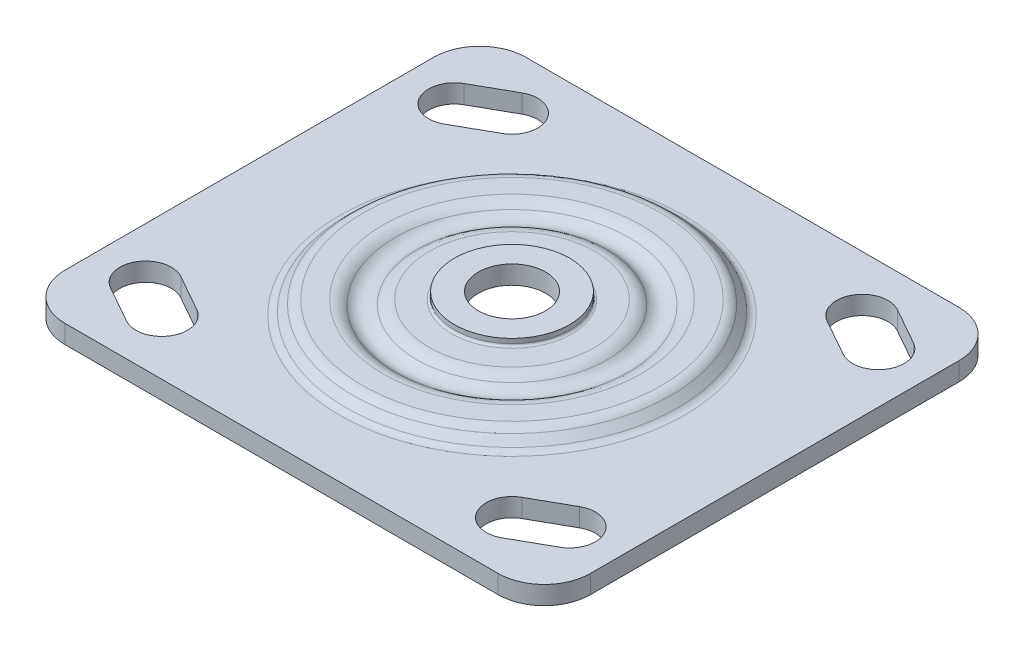
SolidWorks part; units mm, degrees
ref_plane "Front Plane" through (0, 0, 0) normal (0, 0, 1) x (1, 0, 0)
ref_plane "Top Plane" through (0, 0, 0) normal (0, 1, 0) x (1, 0, 0)
ref_plane "Right Plane" through (0, 0, 0) normal (1, 0, 0) x (0, 0, -1)
ref_axis "Axis_X" through (-88.99, 0, 0) along (1, 0, 0)
ref_axis "Axis_Y" through (0, 55, 0) along (0, -1, 0)
ref_axis "Axis_Z" through (0, 0, -88.99) along (0, 0, 1)
sketch "Sketch1" plane through (0, 0, 0) normal (0, 0, 1) x (1, 0, 0)
  line L0 (0, 0) -> (0, 8.505) construction
  line L1 (0, 8.505) -> (-12.5, 8.505)
  line L2 (-12.5, 8.505) -> (-12.5, 7.5)
  line L3 (-13, 7) -> (-18.011, 7)
  line L4 (-27.989, 7) -> (-32.41, 7)
  line L5 (-34.4607, 6.1506) -> (-35.996, 4.6151)
  line L6 (-37.481, 4) -> (-37.481, 0)
  line L7 (-31.747, 3) -> (-28.1759, 3)
  line L8 (-33.168, 1.7863) -> (-32.1005, 2.8536)
  line L9 (-18.011, 3) -> (-13.938, 3)
  line L10 (-12.0015, 4.5) -> (0, 4.5)
  line L11 (0, 8.505) -> (0, 4.5)
  arc A0 (-18.011, 7) -> (-20.6718, 5.9867) centre (-18.011, 3) ccw
  arc A1 (-25.3282, 5.9867) -> (-20.6718, 5.9867) centre (-23, 8.6) ccw
  arc A2 (-25.3282, 5.9867) -> (-27.989, 7) centre (-27.989, 3) ccw
  arc A3 (-37.481, 0) -> (-33.168, 1.7863) centre (-37.481, 6.1) ccw
  arc A4 (-32.41, 7) -> (-34.4607, 6.1506) centre (-32.41, 4.1) ccw
  arc A5 (-31.747, 3) -> (-32.1005, 2.8536) centre (-31.747, 2.5) ccw
  arc A6 (-27.8524, 2.8812) -> (-18.011, 3) centre (-23, 8.6) ccw
  arc A7 (-27.8524, 2.8812) -> (-28.1759, 3) centre (-28.1759, 2.5) ccw
  arc A9 (-13.938, 3) -> (-12.4856, 4.125) centre (-13.938, 4.5) ccw
  arc A10 (-12.0015, 4.5) -> (-12.4856, 4.125) centre (-12.0015, 4) ccw
  arc A11 (-37.481, 4) -> (-35.996, 4.6151) centre (-37.481, 6.1) ccw
  arc A12 (-12.5, 7.5) -> (-13, 7) centre (-13, 7.5) cw
  point P35 (-12.438, 4.5)
  dimension "FIX_3" = 8
  dimension "FIX_5" = 7
  dimension "FIX_7" = 2.9
  dimension "FIX_9" = 12.2
  dimension "FIX_10" = 0.5
  dimension "FIX_12" = 0.5
  dimension "FIX_13" = 3
  dimension "FIX_14" = 0.5
  dimension "FIX_15" = 0.5
  dimension "FIX_16" = 25
  dimension "FIX_1" = 8.505
  dimension "FIX_2" = 7
  dimension "FIX_4" = 18.011
  dimension "FIX_17" = 23
  dimension "FIX_18" = 74.962
  dimension "FIX_6" = 4
  dimension "FIX_8" = 5.071
  dimension "FIX_11" = 5.734
  dimension "FIX_19" = 13.938
revolve "Revolve1" add sketch "Sketch1" angle 360 about L0
sketch "Sketch2" plane through (0, 0, 0) normal (0, 1, 0) x (1, 0, 0)
  line L0 (-46, 33.5) -> (-38, 38) construction
  line L1 (-57, -50) -> (57, -50)
  line L2 (-57, -50) -> (-57, 50)
  line L3 (-57, 50) -> (57, 50)
  line L4 (57, -50) -> (57, 50)
  line L5 (-57, -50) -> (57, 50) construction
  line L6 (-57, 50) -> (57, -50) construction
  line L7 (-48.7455, 38.3808) -> (-40.7455, 42.8808)
  line L8 (-43.2545, 28.6192) -> (-35.2545, 33.1192)
  line L9 (46, -33.5) -> (38, -38) construction
  line L10 (48.7455, -38.3808) -> (40.7455, -42.8808)
  line L11 (43.2545, -28.6192) -> (35.2545, -33.1192)
  line L12 (38, 38) -> (46, 33.5) construction
  line L13 (40.7455, 42.8808) -> (48.7455, 38.3808)
  line L14 (35.2545, 33.1192) -> (43.2545, 28.6192)
  line L15 (-46, -33.5) -> (-38, -38) construction
  line L16 (-43.2545, -28.6192) -> (-35.2545, -33.1192)
  line L17 (-48.7455, -38.3808) -> (-40.7455, -42.8808)
  line L18 (0, 0) -> (57, 0) construction
  line L19 (0, 0) -> (0, 50) construction
  circle A0 centre (0, 0) radius 37.481 construction
  circle A1 centre (0, 0) radius 37.481
  arc A2 (-48.7455, 38.3808) -> (-43.2545, 28.6192) centre (-46, 33.5) ccw
  arc A3 (-35.2545, 33.1192) -> (-40.7455, 42.8808) centre (-38, 38) ccw
  arc A4 (48.7455, -38.3808) -> (43.2545, -28.6192) centre (46, -33.5) ccw
  arc A5 (35.2545, -33.1192) -> (40.7455, -42.8808) centre (38, -38) ccw
  arc A6 (40.7455, 42.8808) -> (35.2545, 33.1192) centre (38, 38) ccw
  arc A7 (43.2545, 28.6192) -> (48.7455, 38.3808) centre (46, 33.5) ccw
  arc A8 (-43.2545, -28.6192) -> (-48.7455, -38.3808) centre (-46, -33.5) ccw
  arc A9 (-40.7455, -42.8808) -> (-35.2545, -33.1192) centre (-38, -38) ccw
  point P9 (-42, 35.75)
  point P16 (42, -35.75)
  point P23 (42, 35.75)
  point P30 (-42, -35.75)
  dimension "FIX_21" = 114
  dimension "FIX_22" = 100
  dimension "FIX_23" = 11.2
  dimension "FIX_24" = 8
  dimension "FIX_25" = 4.5
  dimension "FIX_26" = 67
  dimension "FIX_27" = 76
  dimension "FIX_28" = 76
  dimension "FIX_29" = 67
extrude "Boss-Extrude1" add sketch "Sketch2" along normal blind 4
fillet "Fillet1" radius 10 4 edges at (-57, 2, -50) (57, 2, -50) (57, 2, 50) (-57, 2, 50)
sketch "Sketch3" plane through (0, 8.505, 0) normal (0, 1, 0) x (1, 0, 0)
  circle A0 centre (0, 0) radius 7.3
  dimension "FIX_32" = 14.6
extrude "Cut-Extrude1" cut sketch "Sketch3" against normal through all
equation "\"Factor\"= 1.082532"
